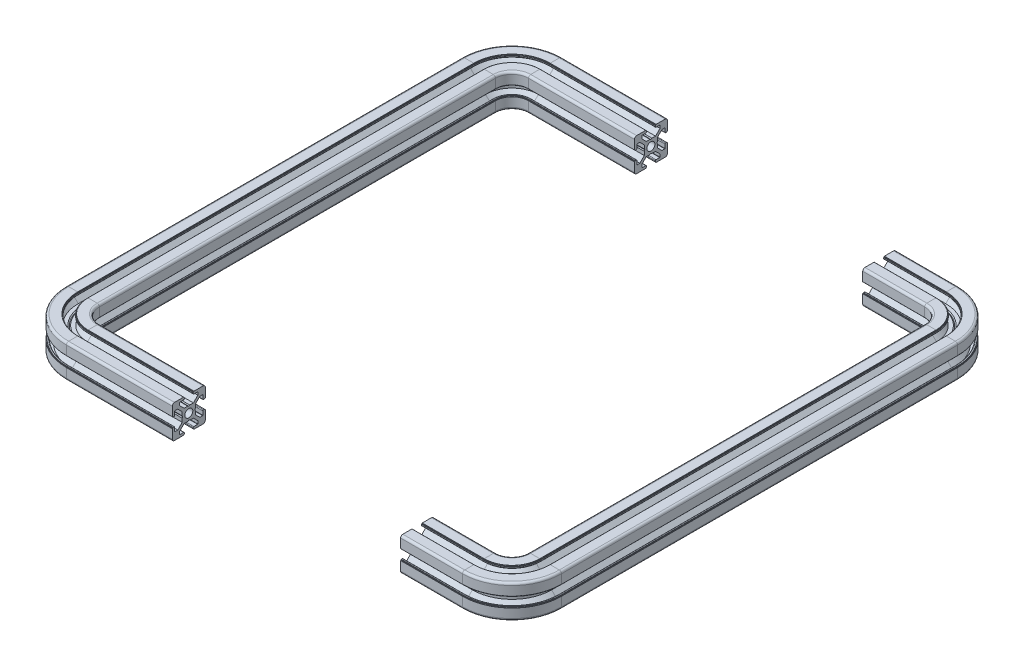
SolidWorks part; units mm, degrees
material "AISI 1020"
ref_plane "Alzado" through (0, 0, 0) normal (0, 0, 1) x (1, 0, 0)
ref_plane "Planta" through (0, 0, 0) normal (0, 1, 0) x (1, 0, 0)
ref_plane "Vista lateral" through (0, 0, 0) normal (1, 0, 0) x (0, 0, -1)
sketch "Croquis1" plane through (0, 0, 0) normal (0, 1, 0) x (1, 0, 0)
  line L5 (-210, 0) -> (210, 0) construction
  line L6 (123.755, -210) -> (180, -210)
  line L10 (210, -180) -> (210, 180)
  line L15 (180, 210) -> (123.755, 210)
  line L17 (-83.755, 210) -> (-180, 210)
  line L18 (-210, 180) -> (-210, -180)
  line L19 (-180, -210) -> (-83.755, -210)
  line L23 (-83.755, 172.9) -> (-83.755, 210)
  line L26 (-83.755, 172.9) -> (123.755, 172.9)
  line L32 (-83.755, -172.9) -> (-83.755, -210)
  line L33 (-83.755, -172.9) -> (123.755, -172.9)
  line L34 (123.755, -172.9) -> (123.755, -210)
  line L38 (123.755, 172.9) -> (123.755, 210)
  line L39 (-170, 210) -> (-170, -210) construction
  line L40 (-170, 92.1045) -> (210, 92.1045) construction
  arc A8 (-180, -210) -> (-210, -180) centre (-180, -180) cw
  arc A9 (210, -180) -> (180, -210) centre (180, -180) cw
  arc A10 (210, 180) -> (180, 210) centre (180, 180) ccw
  arc A11 (-180, 210) -> (-210, 180) centre (-180, 180) ccw
  point P2 (0, 0)
  point P3 (0, 0)
  point P18 (-210, -210)
  point P21 (210, -210)
  point P24 (210, 210)
  point P27 (-210, 210)
  point P32 (20, 92.1045)
  point P35 (20, 172.9)
  point P43 (20, -172.9)
  dimension "D7" = 30
  dimension "D6" = 420
  dimension "D4" = 420
  dimension "D1" = 207.51
  dimension "D2" = 37.1
  dimension "D3" = 380
other "Aluminio BOSCH_PERFIL 30 X 30(16)" corner treatment miter
ref_plane "Plano1" through (-210, 0, -180) normal (0, 0, 1) x (1, 0, 0)
sketch "Sketch1" plane through (-210, 0, -180) normal (0, 0, 1) x (1, 0, 0)
  line L0 (-13, 15) -> (-15, 15) construction
  line L1 (-15, 13) -> (-15, 15) construction
  line L2 (13, 15) -> (15, 15) construction
  line L3 (15, 13) -> (15, 15) construction
  line L4 (-4.75, 15) -> (4.75, 15) construction
  line L5 (-4.75, -15) -> (4.75, -15) construction
  line L6 (-15, 4.75) -> (-15, -4.75) construction
  line L7 (15, 4.75) -> (15, -4.75) construction
  line L8 (-15, -13) -> (-15, -15) construction
  line L9 (-13, -15) -> (-15, -15) construction
  line L10 (15, -13) -> (15, -15) construction
  line L11 (13, -15) -> (15, -15) construction
  line L12 (0, 5.4849) -> (0, 15) construction
  line L13 (0, -5.4849) -> (0, -15) construction
  line L14 (5.4849, 0) -> (15, 0) construction
  line L15 (-5.4849, 0) -> (-15, 0) construction
  line L24 (-0.9, -6) -> (0, -5.4849)
  line L25 (0, -5.4849) -> (0.9, -6)
  line L26 (0.9, -6) -> (4.2045, -6)
  line L27 (4.2045, -6) -> (8.25, -10.05)
  line L28 (8.25, -10.05) -> (8.25, -12.6)
  line L29 (8.05, -12.8) -> (4.65, -12.8)
  line L30 (4.05, -13.4) -> (4.05, -14.3)
  line L31 (4.25, -14.5) -> (4.35, -14.5)
  line L32 (4.55, -14.7) -> (4.55, -14.8)
  line L33 (4.75, -15) -> (13, -15)
  line L34 (15, -13) -> (15, -4.75)
  line L35 (14.8, -4.55) -> (14.7, -4.55)
  line L36 (14.5, -4.35) -> (14.5, -4.25)
  line L37 (14.3, -4.05) -> (13.4, -4.05)
  line L38 (12.8, -4.65) -> (12.8, -8.05)
  line L39 (12.6, -8.25) -> (10.05, -8.25)
  line L40 (10.05, -8.25) -> (6.0045, -4.2045)
  line L41 (6.0045, -4.2045) -> (6.0045, -0.9)
  line L42 (6.0045, -0.9) -> (5.4849, 0)
  line L43 (5.4849, 0) -> (6.0045, 0.9)
  line L44 (6.0045, 0.9) -> (6.0045, 4.2045)
  line L45 (6.0045, 4.2045) -> (10.05, 8.25)
  line L46 (10.05, 8.25) -> (12.6, 8.25)
  line L47 (12.8, 8.05) -> (12.8, 4.65)
  line L48 (13.4, 4.05) -> (14.3, 4.05)
  line L49 (14.5, 4.25) -> (14.5, 4.35)
  line L50 (14.7, 4.55) -> (14.8, 4.55)
  line L51 (15, 4.75) -> (15, 13)
  line L52 (13, 15) -> (4.75, 15)
  line L53 (4.55, 14.8) -> (4.55, 14.7)
  line L54 (4.35, 14.5) -> (4.25, 14.5)
  line L55 (4.05, 14.3) -> (4.05, 13.4)
  line L56 (4.65, 12.8) -> (8.05, 12.8)
  line L57 (8.25, 12.6) -> (8.25, 10.05)
  line L58 (8.25, 10.05) -> (4.2045, 6)
  line L59 (4.2045, 6) -> (0.9, 6)
  line L60 (0.9, 6) -> (0, 5.4849)
  line L61 (0, 5.4849) -> (-0.9, 6)
  line L62 (-0.9, 6) -> (-4.2045, 6)
  line L63 (-4.2045, 6) -> (-8.25, 10.05)
  line L64 (-8.25, 10.05) -> (-8.25, 12.6)
  line L65 (-8.05, 12.8) -> (-4.65, 12.8)
  line L66 (-4.05, 13.4) -> (-4.05, 14.3)
  line L67 (-4.25, 14.5) -> (-4.35, 14.5)
  line L68 (-4.55, 14.7) -> (-4.55, 14.8)
  line L69 (-4.75, 15) -> (-13, 15)
  line L70 (-15, 13) -> (-15, 4.75)
  line L71 (-14.8, 4.55) -> (-14.7, 4.55)
  line L72 (-14.5, 4.35) -> (-14.5, 4.25)
  line L73 (-14.3, 4.05) -> (-13.4, 4.05)
  line L74 (-12.8, 4.65) -> (-12.8, 8.05)
  line L75 (-12.6, 8.25) -> (-10.05, 8.25)
  line L76 (-10.05, 8.25) -> (-6.0045, 4.2045)
  line L77 (-6.0045, 4.2045) -> (-6.0045, 0.9)
  line L78 (-6.0045, 0.9) -> (-5.4849, 0)
  line L79 (-5.4849, 0) -> (-6.0045, -0.9)
  line L80 (-6.0045, -0.9) -> (-6.0045, -4.2045)
  line L81 (-6.0045, -4.2045) -> (-10.05, -8.25)
  line L82 (-10.05, -8.25) -> (-12.6, -8.25)
  line L83 (-12.8, -8.05) -> (-12.8, -4.65)
  line L84 (-13.4, -4.05) -> (-14.3, -4.05)
  line L85 (-14.5, -4.25) -> (-14.5, -4.35)
  line L86 (-14.7, -4.55) -> (-14.8, -4.55)
  line L87 (-15, -4.75) -> (-15, -13)
  line L88 (-13, -15) -> (-4.75, -15)
  line L89 (-4.55, -14.8) -> (-4.55, -14.7)
  line L90 (-4.35, -14.5) -> (-4.25, -14.5)
  line L91 (-4.05, -14.3) -> (-4.05, -13.4)
  line L92 (-4.65, -12.8) -> (-8.05, -12.8)
  line L93 (-8.25, -12.6) -> (-8.25, -10.05)
  line L94 (-8.25, -10.05) -> (-4.2045, -6)
  line L95 (-4.2045, -6) -> (-0.9, -6)
  circle A0 centre (0, 0) radius 3.65
  arc A20 (8.05, -12.8) -> (8.25, -12.6) centre (8.05, -12.6) ccw
  arc A21 (4.65, -12.8) -> (4.05, -13.4) centre (4.65, -13.4) ccw
  arc A22 (4.05, -14.3) -> (4.25, -14.5) centre (4.25, -14.3) ccw
  arc A23 (4.55, -14.7) -> (4.35, -14.5) centre (4.35, -14.7) ccw
  arc A24 (4.55, -14.8) -> (4.75, -15) centre (4.75, -14.8) ccw
  arc A25 (13, -15) -> (15, -13) centre (13, -13) ccw
  arc A26 (15, -4.75) -> (14.8, -4.55) centre (14.8, -4.75) ccw
  arc A27 (14.5, -4.35) -> (14.7, -4.55) centre (14.7, -4.35) ccw
  arc A28 (14.5, -4.25) -> (14.3, -4.05) centre (14.3, -4.25) ccw
  arc A29 (13.4, -4.05) -> (12.8, -4.65) centre (13.4, -4.65) ccw
  arc A30 (12.6, -8.25) -> (12.8, -8.05) centre (12.6, -8.05) ccw
  arc A31 (12.8, 8.05) -> (12.6, 8.25) centre (12.6, 8.05) ccw
  arc A32 (12.8, 4.65) -> (13.4, 4.05) centre (13.4, 4.65) ccw
  arc A33 (14.3, 4.05) -> (14.5, 4.25) centre (14.3, 4.25) ccw
  arc A34 (14.7, 4.55) -> (14.5, 4.35) centre (14.7, 4.35) ccw
  arc A35 (14.8, 4.55) -> (15, 4.75) centre (14.8, 4.75) ccw
  arc A36 (15, 13) -> (13, 15) centre (13, 13) ccw
  arc A37 (4.75, 15) -> (4.55, 14.8) centre (4.75, 14.8) ccw
  arc A38 (4.35, 14.5) -> (4.55, 14.7) centre (4.35, 14.7) ccw
  arc A39 (4.25, 14.5) -> (4.05, 14.3) centre (4.25, 14.3) ccw
  arc A40 (4.05, 13.4) -> (4.65, 12.8) centre (4.65, 13.4) ccw
  arc A41 (8.25, 12.6) -> (8.05, 12.8) centre (8.05, 12.6) ccw
  arc A42 (-8.05, 12.8) -> (-8.25, 12.6) centre (-8.05, 12.6) ccw
  arc A43 (-4.65, 12.8) -> (-4.05, 13.4) centre (-4.65, 13.4) ccw
  arc A44 (-4.05, 14.3) -> (-4.25, 14.5) centre (-4.25, 14.3) ccw
  arc A45 (-4.55, 14.7) -> (-4.35, 14.5) centre (-4.35, 14.7) ccw
  arc A46 (-4.55, 14.8) -> (-4.75, 15) centre (-4.75, 14.8) ccw
  arc A47 (-13, 15) -> (-15, 13) centre (-13, 13) ccw
  arc A48 (-15, 4.75) -> (-14.8, 4.55) centre (-14.8, 4.75) ccw
  arc A49 (-14.5, 4.35) -> (-14.7, 4.55) centre (-14.7, 4.35) ccw
  arc A50 (-14.5, 4.25) -> (-14.3, 4.05) centre (-14.3, 4.25) ccw
  arc A51 (-13.4, 4.05) -> (-12.8, 4.65) centre (-13.4, 4.65) ccw
  arc A52 (-12.6, 8.25) -> (-12.8, 8.05) centre (-12.6, 8.05) ccw
  arc A53 (-12.8, -8.05) -> (-12.6, -8.25) centre (-12.6, -8.05) ccw
  arc A54 (-12.8, -4.65) -> (-13.4, -4.05) centre (-13.4, -4.65) ccw
  arc A55 (-14.3, -4.05) -> (-14.5, -4.25) centre (-14.3, -4.25) ccw
  arc A56 (-14.7, -4.55) -> (-14.5, -4.35) centre (-14.7, -4.35) ccw
  arc A57 (-14.8, -4.55) -> (-15, -4.75) centre (-14.8, -4.75) ccw
  arc A58 (-15, -13) -> (-13, -15) centre (-13, -13) ccw
  arc A59 (-4.75, -15) -> (-4.55, -14.8) centre (-4.75, -14.8) ccw
  arc A60 (-4.35, -14.5) -> (-4.55, -14.7) centre (-4.35, -14.7) ccw
  arc A61 (-4.25, -14.5) -> (-4.05, -14.3) centre (-4.25, -14.3) ccw
  arc A62 (-4.05, -13.4) -> (-4.65, -12.8) centre (-4.65, -13.4) ccw
  arc A63 (-8.25, -12.6) -> (-8.05, -12.8) centre (-8.05, -12.6) ccw
  point P9 (-15, 15)
  point P11 (0, 15)
  point P14 (15, 15)
  point P20 (0, -15)
  point P26 (-15, 0)
  point P30 (15, 0)
  point P32 (-15, -15)
  point P35 (15, -15)
  point P39 (0, 0)
other "Aluminio BOSCH_PERFIL 30 X 30(17)" corner treatment miter
ref_plane "Plano2" through (180, 0, -210) normal (-1, 0, 0) x (0, 0, 1)
sketch "Sketch11" plane through (180, 0, -210) normal (-1, 0, 0) x (0, 0, 1)
  line L0 (-13, 15) -> (-15, 15) construction
  line L1 (-15, 13) -> (-15, 15) construction
  line L2 (13, 15) -> (15, 15) construction
  line L3 (15, 13) -> (15, 15) construction
  line L4 (-4.75, 15) -> (4.75, 15) construction
  line L5 (-4.75, -15) -> (4.75, -15) construction
  line L6 (-15, 4.75) -> (-15, -4.75) construction
  line L7 (15, 4.75) -> (15, -4.75) construction
  line L8 (-15, -13) -> (-15, -15) construction
  line L9 (-13, -15) -> (-15, -15) construction
  line L10 (15, -13) -> (15, -15) construction
  line L11 (13, -15) -> (15, -15) construction
  line L12 (0, 5.4849) -> (0, 15) construction
  line L13 (0, -5.4849) -> (0, -15) construction
  line L14 (5.4849, 0) -> (15, 0) construction
  line L15 (-5.4849, 0) -> (-15, 0) construction
  line L24 (-0.9, -6) -> (0, -5.4849)
  line L25 (0, -5.4849) -> (0.9, -6)
  line L26 (0.9, -6) -> (4.2045, -6)
  line L27 (4.2045, -6) -> (8.25, -10.05)
  line L28 (8.25, -10.05) -> (8.25, -12.6)
  line L29 (8.05, -12.8) -> (4.65, -12.8)
  line L30 (4.05, -13.4) -> (4.05, -14.3)
  line L31 (4.25, -14.5) -> (4.35, -14.5)
  line L32 (4.55, -14.7) -> (4.55, -14.8)
  line L33 (4.75, -15) -> (13, -15)
  line L34 (15, -13) -> (15, -4.75)
  line L35 (14.8, -4.55) -> (14.7, -4.55)
  line L36 (14.5, -4.35) -> (14.5, -4.25)
  line L37 (14.3, -4.05) -> (13.4, -4.05)
  line L38 (12.8, -4.65) -> (12.8, -8.05)
  line L39 (12.6, -8.25) -> (10.05, -8.25)
  line L40 (10.05, -8.25) -> (6.0045, -4.2045)
  line L41 (6.0045, -4.2045) -> (6.0045, -0.9)
  line L42 (6.0045, -0.9) -> (5.4849, 0)
  line L43 (5.4849, 0) -> (6.0045, 0.9)
  line L44 (6.0045, 0.9) -> (6.0045, 4.2045)
  line L45 (6.0045, 4.2045) -> (10.05, 8.25)
  line L46 (10.05, 8.25) -> (12.6, 8.25)
  line L47 (12.8, 8.05) -> (12.8, 4.65)
  line L48 (13.4, 4.05) -> (14.3, 4.05)
  line L49 (14.5, 4.25) -> (14.5, 4.35)
  line L50 (14.7, 4.55) -> (14.8, 4.55)
  line L51 (15, 4.75) -> (15, 13)
  line L52 (13, 15) -> (4.75, 15)
  line L53 (4.55, 14.8) -> (4.55, 14.7)
  line L54 (4.35, 14.5) -> (4.25, 14.5)
  line L55 (4.05, 14.3) -> (4.05, 13.4)
  line L56 (4.65, 12.8) -> (8.05, 12.8)
  line L57 (8.25, 12.6) -> (8.25, 10.05)
  line L58 (8.25, 10.05) -> (4.2045, 6)
  line L59 (4.2045, 6) -> (0.9, 6)
  line L60 (0.9, 6) -> (0, 5.4849)
  line L61 (0, 5.4849) -> (-0.9, 6)
  line L62 (-0.9, 6) -> (-4.2045, 6)
  line L63 (-4.2045, 6) -> (-8.25, 10.05)
  line L64 (-8.25, 10.05) -> (-8.25, 12.6)
  line L65 (-8.05, 12.8) -> (-4.65, 12.8)
  line L66 (-4.05, 13.4) -> (-4.05, 14.3)
  line L67 (-4.25, 14.5) -> (-4.35, 14.5)
  line L68 (-4.55, 14.7) -> (-4.55, 14.8)
  line L69 (-4.75, 15) -> (-13, 15)
  line L70 (-15, 13) -> (-15, 4.75)
  line L71 (-14.8, 4.55) -> (-14.7, 4.55)
  line L72 (-14.5, 4.35) -> (-14.5, 4.25)
  line L73 (-14.3, 4.05) -> (-13.4, 4.05)
  line L74 (-12.8, 4.65) -> (-12.8, 8.05)
  line L75 (-12.6, 8.25) -> (-10.05, 8.25)
  line L76 (-10.05, 8.25) -> (-6.0045, 4.2045)
  line L77 (-6.0045, 4.2045) -> (-6.0045, 0.9)
  line L78 (-6.0045, 0.9) -> (-5.4849, 0)
  line L79 (-5.4849, 0) -> (-6.0045, -0.9)
  line L80 (-6.0045, -0.9) -> (-6.0045, -4.2045)
  line L81 (-6.0045, -4.2045) -> (-10.05, -8.25)
  line L82 (-10.05, -8.25) -> (-12.6, -8.25)
  line L83 (-12.8, -8.05) -> (-12.8, -4.65)
  line L84 (-13.4, -4.05) -> (-14.3, -4.05)
  line L85 (-14.5, -4.25) -> (-14.5, -4.35)
  line L86 (-14.7, -4.55) -> (-14.8, -4.55)
  line L87 (-15, -4.75) -> (-15, -13)
  line L88 (-13, -15) -> (-4.75, -15)
  line L89 (-4.55, -14.8) -> (-4.55, -14.7)
  line L90 (-4.35, -14.5) -> (-4.25, -14.5)
  line L91 (-4.05, -14.3) -> (-4.05, -13.4)
  line L92 (-4.65, -12.8) -> (-8.05, -12.8)
  line L93 (-8.25, -12.6) -> (-8.25, -10.05)
  line L94 (-8.25, -10.05) -> (-4.2045, -6)
  line L95 (-4.2045, -6) -> (-0.9, -6)
  circle A0 centre (0, 0) radius 3.65
  arc A20 (8.05, -12.8) -> (8.25, -12.6) centre (8.05, -12.6) ccw
  arc A21 (4.65, -12.8) -> (4.05, -13.4) centre (4.65, -13.4) ccw
  arc A22 (4.05, -14.3) -> (4.25, -14.5) centre (4.25, -14.3) ccw
  arc A23 (4.55, -14.7) -> (4.35, -14.5) centre (4.35, -14.7) ccw
  arc A24 (4.55, -14.8) -> (4.75, -15) centre (4.75, -14.8) ccw
  arc A25 (13, -15) -> (15, -13) centre (13, -13) ccw
  arc A26 (15, -4.75) -> (14.8, -4.55) centre (14.8, -4.75) ccw
  arc A27 (14.5, -4.35) -> (14.7, -4.55) centre (14.7, -4.35) ccw
  arc A28 (14.5, -4.25) -> (14.3, -4.05) centre (14.3, -4.25) ccw
  arc A29 (13.4, -4.05) -> (12.8, -4.65) centre (13.4, -4.65) ccw
  arc A30 (12.6, -8.25) -> (12.8, -8.05) centre (12.6, -8.05) ccw
  arc A31 (12.8, 8.05) -> (12.6, 8.25) centre (12.6, 8.05) ccw
  arc A32 (12.8, 4.65) -> (13.4, 4.05) centre (13.4, 4.65) ccw
  arc A33 (14.3, 4.05) -> (14.5, 4.25) centre (14.3, 4.25) ccw
  arc A34 (14.7, 4.55) -> (14.5, 4.35) centre (14.7, 4.35) ccw
  arc A35 (14.8, 4.55) -> (15, 4.75) centre (14.8, 4.75) ccw
  arc A36 (15, 13) -> (13, 15) centre (13, 13) ccw
  arc A37 (4.75, 15) -> (4.55, 14.8) centre (4.75, 14.8) ccw
  arc A38 (4.35, 14.5) -> (4.55, 14.7) centre (4.35, 14.7) ccw
  arc A39 (4.25, 14.5) -> (4.05, 14.3) centre (4.25, 14.3) ccw
  arc A40 (4.05, 13.4) -> (4.65, 12.8) centre (4.65, 13.4) ccw
  arc A41 (8.25, 12.6) -> (8.05, 12.8) centre (8.05, 12.6) ccw
  arc A42 (-8.05, 12.8) -> (-8.25, 12.6) centre (-8.05, 12.6) ccw
  arc A43 (-4.65, 12.8) -> (-4.05, 13.4) centre (-4.65, 13.4) ccw
  arc A44 (-4.05, 14.3) -> (-4.25, 14.5) centre (-4.25, 14.3) ccw
  arc A45 (-4.55, 14.7) -> (-4.35, 14.5) centre (-4.35, 14.7) ccw
  arc A46 (-4.55, 14.8) -> (-4.75, 15) centre (-4.75, 14.8) ccw
  arc A47 (-13, 15) -> (-15, 13) centre (-13, 13) ccw
  arc A48 (-15, 4.75) -> (-14.8, 4.55) centre (-14.8, 4.75) ccw
  arc A49 (-14.5, 4.35) -> (-14.7, 4.55) centre (-14.7, 4.35) ccw
  arc A50 (-14.5, 4.25) -> (-14.3, 4.05) centre (-14.3, 4.25) ccw
  arc A51 (-13.4, 4.05) -> (-12.8, 4.65) centre (-13.4, 4.65) ccw
  arc A52 (-12.6, 8.25) -> (-12.8, 8.05) centre (-12.6, 8.05) ccw
  arc A53 (-12.8, -8.05) -> (-12.6, -8.25) centre (-12.6, -8.05) ccw
  arc A54 (-12.8, -4.65) -> (-13.4, -4.05) centre (-13.4, -4.65) ccw
  arc A55 (-14.3, -4.05) -> (-14.5, -4.25) centre (-14.3, -4.25) ccw
  arc A56 (-14.7, -4.55) -> (-14.5, -4.35) centre (-14.7, -4.35) ccw
  arc A57 (-14.8, -4.55) -> (-15, -4.75) centre (-14.8, -4.75) ccw
  arc A58 (-15, -13) -> (-13, -15) centre (-13, -13) ccw
  arc A59 (-4.75, -15) -> (-4.55, -14.8) centre (-4.75, -14.8) ccw
  arc A60 (-4.35, -14.5) -> (-4.55, -14.7) centre (-4.35, -14.7) ccw
  arc A61 (-4.25, -14.5) -> (-4.05, -14.3) centre (-4.25, -14.3) ccw
  arc A62 (-4.05, -13.4) -> (-4.65, -12.8) centre (-4.65, -13.4) ccw
  arc A63 (-8.25, -12.6) -> (-8.05, -12.8) centre (-8.05, -12.6) ccw
  point P9 (-15, 15)
  point P11 (0, 15)
  point P14 (15, 15)
  point P20 (0, -15)
  point P26 (-15, 0)
  point P30 (15, 0)
  point P32 (-15, -15)
  point P35 (15, -15)
  point P39 (0, 0)
equation "\"Ancho_llanta\"= 44mm"
equation "\"Diametro_llanta\"= 197.51mm"
equation "\"D1@Croquis1\"=\"Diametro_llanta\"+10"
equation "\"D2@Croquis1\"=\"Ancho_llanta\" - 15 + 8.1"
